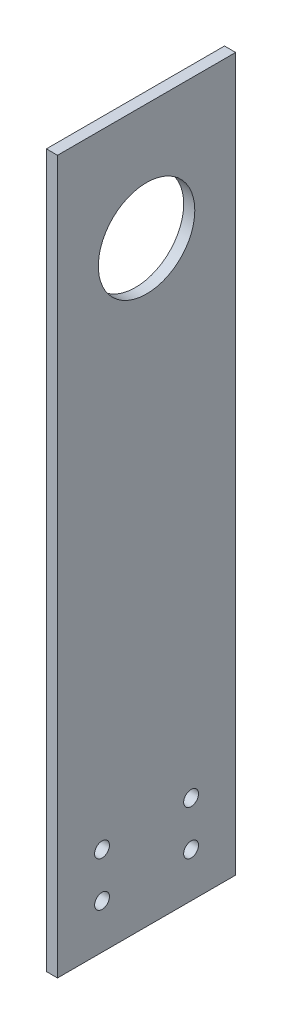
SolidWorks part; units mm, degrees
material "6061 Alloy"
ref_plane "Front Plane" through (0, 0, 0) normal (0, 0, 1) x (1, 0, 0)
ref_plane "Top Plane" through (0, 0, 0) normal (0, 1, 0) x (1, 0, 0)
ref_plane "Right Plane" through (0, 0, 0) normal (1, 0, 0) x (0, 0, -1)
sketch "Sketch1" plane through (0, 0, 0) normal (1, 0, 0) x (0, 0, -1)
  line L1 (-38.1, 152.4) -> (38.1, 152.4)
  line L2 (-38.1, 152.4) -> (-38.1, -152.4)
  line L3 (-38.1, -152.4) -> (38.1, -152.4)
  line L4 (38.1, 152.4) -> (38.1, -152.4)
  line L5 (-38.1, 152.4) -> (38.1, -152.4) construction
  line L6 (-38.1, -152.4) -> (38.1, 152.4) construction
  point P0 (0, 0)
  dimension "D1" = 304.8
  dimension "D2" = 76.2
extrude "Boss-Extrude1" add sketch "Sketch1" along normal blind 4.7625
sketch "Sketch2" plane through (4.7625, 0, 0) normal (1, 0, 0) x (0, 0, -1)
  line L0 (-38.1, -152.4) -> (38.1, -152.4) construction
  line L1 (-38.1, 152.4) -> (-38.1, -152.4) construction
  circle A0 centre (0, 102.616) radius 20.6375
  dimension "D1" = 255.016
  dimension "D2" = 38.1
  dimension "D3" = 41.275
extrude "Cut-Extrude1" cut sketch "Sketch2" against normal up to next
sketch "Sketch4" plane through (4.7625, 0, 0) normal (1, 0, 0) x (0, 0, -1)
  line L0 (-38.1, 152.4) -> (-38.1, -152.4) construction
  line L1 (-38.1, -152.4) -> (38.1, -152.4) construction
  circle A0 centre (-19.05, -114.3) radius 3.175
  circle A1 centre (19.05, -114.3) radius 3.175
  circle A2 centre (19.05, -133.35) radius 3.175
  circle A3 centre (-19.05, -133.35) radius 3.175
  dimension "D1" = 19.05
  dimension "D2" = 6.35
  dimension "D3" = 38.1
  dimension "D5" = 2
  dimension "D4" = 2
extrude "Cut-Extrude2" cut sketch "Sketch4" against normal up to next
